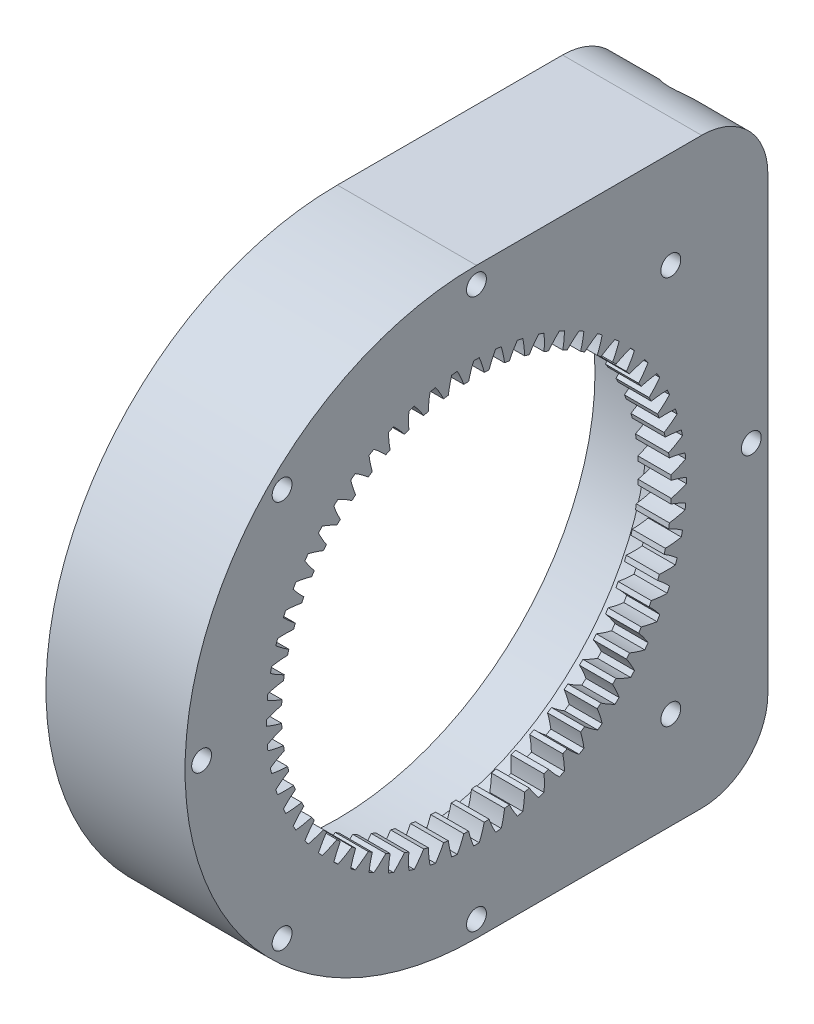
SolidWorks part; units mm, degrees
ref_plane "Plane1" through (0, 0, 0) normal (0, 0, 1) x (1, 0, 0)
ref_plane "Plane2" through (0, 0, 0) normal (0, 1, 0) x (1, 0, 0)
ref_plane "Plane3" through (0, 0, 0) normal (1, 0, 0) x (0, 0, -1)
other "Configuration Table"
sketch "HoldingSke" plane through (0, 0, 0) normal (0, 1, 0) x (1, 0, 0)
  line L0 (0, 0) -> (0.4926, -0.8532)
  line L1 (-15, 0) -> (100, 0) construction
  line L2 (0, 0) -> (-2.1039, 2.3779)
  line L3 (0, 0) -> (-11.863, 4.5341)
  line L4 (0, 0) -> (4.318, 7.479)
  line L5 (0, 0) -> (-23.7986, -8.8762)
  line L6 (0, 0) -> (-10.5278, -7.1032)
  line L7 (-2.1039, 2.3779) -> (3.3635, 27.1825)
  line L8 (-76.2, 3.3929) -> (-54.61, 3.3929)
  line L9 (-67.7845, 28.3722) -> (-49.3413, 33.142)
  line L10 (-76.2, 71.12) -> (104.1128, 71.12)
  line L11 (0, 0) -> (-5, 0)
  line L12 (-76.2, 101.6) -> (-76.162, 101.6)
  line L13 (24.9733, 27.94) -> (52.9518, 28.4284)
  line L14 (24.9733, 27.94) -> (24.9743, 27.94)
  line L15 (24.9733, 27.94) -> (100.4006, 29.5858)
  circle A0 centre (0, 0) radius 44
  circle A1 centre (0, 0) radius 12.7
  circle A2 centre (0, 0) radius 12.7
  dimension "Num_teeth" = 60
  dimension "Pitch_radius" = 180.3128
  dimension "Width" = 5
  dimension "Diameter" = 88
sketch "BasProSke" plane through (0, 0, 0) normal (0, 1, 0) x (1, 0, 0)
  line L0 (-10, 0) -> (60, 0) construction
  line L1 (0, 29.435) -> (0, 44)
  line L2 (0, 29.435) -> (5, 29.435)
  line L3 (5, 29.435) -> (5, 44)
  line L4 (5, 44) -> (0, 44)
  dimension "Thickness" = 5
  dimension "Diameter" = 88
revolve "Base-Revolve" add sketch "BasProSke" angle 360 about L0
sketch "TooCutSke" plane through (0, 0, 0) normal (1, 0, 0) x (0, 0, -1)
  line L3 (0.8921, 30.4369) -> (0.8921, 53.6633) construction
  line L4 (0, 0) -> (0, 59.563) construction
  line L5 (0, 0) -> (-3.576, 68.2339) construction
  line L6 (-13.6269, 25.8543) -> (36.4024, 28.4763) construction
  circle A0 centre (0, 0) radius 30.45 construction
  circle A1 centre (0, 0) radius 31.7197 construction
  circle A2 centre (0, 0) radius 26.5321 construction
  circle A3 centre (0, 0) radius 29.4096 construction
  arc A4 (1.1829, 29.3858) -> (0.4241, 31.7169) centre (-13.6269, 25.8543) ccw
  arc A5 (1.1829, 29.3858) -> (-1.1829, 29.3858) centre (0, 0) ccw
  arc A6 (0.4241, 31.7169) -> (-0.4241, 31.7169) centre (0, 0) ccw
  arc A7 (-0.4241, 31.7169) -> (-1.1829, 29.3858) centre (13.6269, 25.8543) ccw
extrude "ToothCut" cut sketch "TooCutSke" along normal through all
fillet "Breaks" [suppressed] radius 0.1015
fillet "RootFillets" [suppressed] radius 0.2547
pattern_circular "TeethCuts" count 60 every 6 about axis through (-10, 0, 0) along (1, 0, 0) of "RootFillets", "Breaks", "ToothCut"
sketch "Sketch4" plane through (0, 0, 0) normal (-1, 0, 0) x (0, 0, 1)
  circle A0 centre (0, 0) radius 44
  circle A1 centre (0, 0) radius 38.9
  circle A2 centre (0, 0) radius 44 construction
  dimension "D1" = 77.8
extrude "Boss-Extrude3" add sketch "Sketch4" along normal blind 16
sketch "Sketch7" plane through (5, 0, 0) normal (1, 0, 0) x (0, 0, -1)
  line L0 (0, 44) -> (44, 44)
  line L1 (44, 44) -> (44, 0)
  circle A0 centre (0, 0) radius 44 construction
  arc A1 (44, 0) -> (0, 44) centre (0, 0) ccw
extrude "Boss-Extrude5" add sketch "Sketch7" against normal up to surface (21 mm away) up to face at (-16, 0, 44)
sketch "Sketch10" plane through (5, 0, 0) normal (1, 0, 0) x (0, 0, -1)
  line L0 (0, -44) -> (44, -44)
  line L1 (44, -44) -> (44, 0)
  line L2 (44, 0) -> (44, 44) construction
  circle A0 centre (0, 0) radius 44 construction
  arc A1 (0, -44) -> (44, 0) centre (0, 0) ccw
  dimension "D1" = 180
extrude "Boss-Extrude6" add sketch "Sketch10" against normal up to surface (21 mm away) up to face at (-16, 11.6291, -11.6291)
fillet "Fillet1" radius 10 2 edges at (-5.5, 44, -44) (-5.5, -44, -44)
sketch "Sketch14" plane through (0, 0, 0) normal (-1, 0, 0) x (0, 0, 1)
  circle A0 centre (0, 0) radius 36.9
  circle A1 centre (0, 0) radius 38.9 construction
  circle A2 centre (0, 0) radius 38.9
  dimension "D1" = 2
extrude "Boss-Extrude7" add sketch "Sketch14" along normal blind 6
sketch "Sketch15" plane through (0, 0, -44) normal (0, 0, -1) x (-1, 0, 0)
  line L0 (-5, -34) -> (16, -34) construction
  line L1 (16, -44) -> (-5, -44) construction
  line L2 (-5, 44) -> (16, 44) construction
  circle A0 centre (5.5, -38) radius 4.25
  circle A1 centre (5.5, 38) radius 4.25
  point P4 (5.5, -34)
  point P5 (0, 0)
  dimension "D1" = 8.5
  dimension "D2" = 6
  dimension "D3" = 6
extrude "Cut-Extrude1" cut sketch "Sketch15" against normal blind 20
chamfer "Chamfer1" distance 10 angle 1 2 edges at (-9.75, 38, -24) (-9.75, -38, -24) first distance on face at (-5.612, 37.997, -41.83) first distance on face at (-5.388, -37.997, -41.83)
sketch "Sketch16" plane through (-16, 0, 0) normal (-1, 0, 0) x (0, 0, 1)
  circle A0 centre (41.5, 0) radius 1.5
  point P2 (0, 0)
  point P4 (0, 0)
  dimension "D2" = 3
  dimension "D1" = 41.5
extrude "Cut-Extrude3" cut sketch "Sketch16" against normal blind 30
pattern_circular "CirPattern1" count 8 over 360 about axis through (-10, 0, 0) along (-1, 0, 0) of "Cut-Extrude3"
equation "' \"Module@HoldingSke\" = 6.35"
equation "' \"Num_teeth@HoldingSke\" = 24"
equation "' \"Ap@HoldingSke\" =  14.5"
equation "' \"Ap@HoldingSke\" = 14.5"
equation "' \"Width@HoldingSke\" = 12"
equation "' \"Diameter@HoldingSke\" = 8 * 25.4"
equation "' \"Show_teeth@HoldingSke\" = 100"
equation "' \"Backlash@HoldingSke\" = 0.009 * 25.4"
equation "' \"Addendum_fac@HoldingSke\" = 1.0"
equation "' \"Dedendum_fac@HoldingSke\" = 1.25"
equation "' \"Dedendum_add@HoldingSke\" = 0.00005 * 25.4"
equation "' \"Clearance_fac@HoldingSke\" = 0.25"
equation "\"Pitch@HoldingSke\" = 1 / \"Module@HoldingSke\" "
equation "\"Overcut_dia@TooCutSke\" = (\"Num_teeth@HoldingSke\" - 2 * \"Addendum_fac@HoldingSke\") / \"Pitch@HoldingSke\" - 0.002 * 25.4"
equation "\"Pitch_dia@TooCutSke\" = \"Num_teeth@HoldingSke\" / \"Pitch@HoldingSke\""
equation "\"Base_dia@TooCutSke\" = \"Num_teeth@HoldingSke\" / \"Pitch@HoldingSke\" * cos((\"Ap@HoldingSke\"  * 3.14159265 / 180)) * 0.90"
equation "\"Root_dia@TooCutSke\" = \"Num_teeth@HoldingSke\"  / \"Pitch@HoldingSke\" + 2 *  \"Dedendum_fac@HoldingSke\"/ \"Pitch@HoldingSke\" + \"Dedendum_add@HoldingSke\" * 2"
equation "\"Half_ang@TooCutSke\" = 180 / \"Num_teeth@HoldingSke\""
equation "\"Half_CT@TooCutSke\" = \"Num_teeth@HoldingSke\" / \"Pitch@HoldingSke\" * sin((3.14159265 / 2 / \"Num_teeth@HoldingSke\")) / 2 + 10 * \"Backlash@HoldingSke\" / 4"
equation "\"Flank_rad@TooCutSke\" = \"Num_teeth@HoldingSke\" / \"Pitch@HoldingSke\" / 4"
equation "\"Radius@RootFillets\"= \"Clearance_fac@HoldingSke\" / \"Pitch@HoldingSke\" + \"Dedendum_add@HoldingSke\""
equation "\"Break_rad@Breaks\" = 0.02 / \"Pitch@HoldingSke\" * 5"
equation "\"Num_teeth@TeethCuts\" = int( \"Show_teeth@HoldingSke\" ) + 1"
equation "\"Num_teeth@TeethCuts\" = ((sgn( \"Num_teeth@TeethCuts\" - \"Num_teeth@HoldingSke\" )-1)*( \"Num_teeth@TeethCuts\" - \"Num_teeth@HoldingSke\" ))/-2+ \"Num_teeth@HoldingSke\""
equation "\"Num_teeth@TeethCuts\" = ((sgn( \"Num_teeth@TeethCuts\" - 2.0)+1)*( \"Num_teeth@TeethCuts\" - 2.0))/2 +2.0"
equation "\"Angle@TeethCuts\" = 360.0 / \"Num_teeth@HoldingSke\""
equation "\"Diameter@BasProSke\" = \"Num_teeth@HoldingSke\"  / \"Pitch@HoldingSke\" + 2 *  \"Dedendum_fac@HoldingSke\"/ \"Pitch@HoldingSke\" + \"Dedendum_add@HoldingSke\" * 2 + 0.002 * 25.4"
equation "\"Diameter@BasProSke\" = ((sgn( \"Diameter@BasProSke\"  - \"Diameter@HoldingSke\" )+1)*( \"Diameter@BasProSke\"  - \"Diameter@HoldingSke\" ))/2 + \"Diameter@HoldingSke\""
equation "\"Inside_diameter@BasProSke\" =  (\"Num_teeth@HoldingSke\" - 2 * \"Addendum_fac@HoldingSke\") / \"Pitch@HoldingSke\" "
equation "\"Thickness@BasProSke\"  = \"Width@HoldingSke\""
